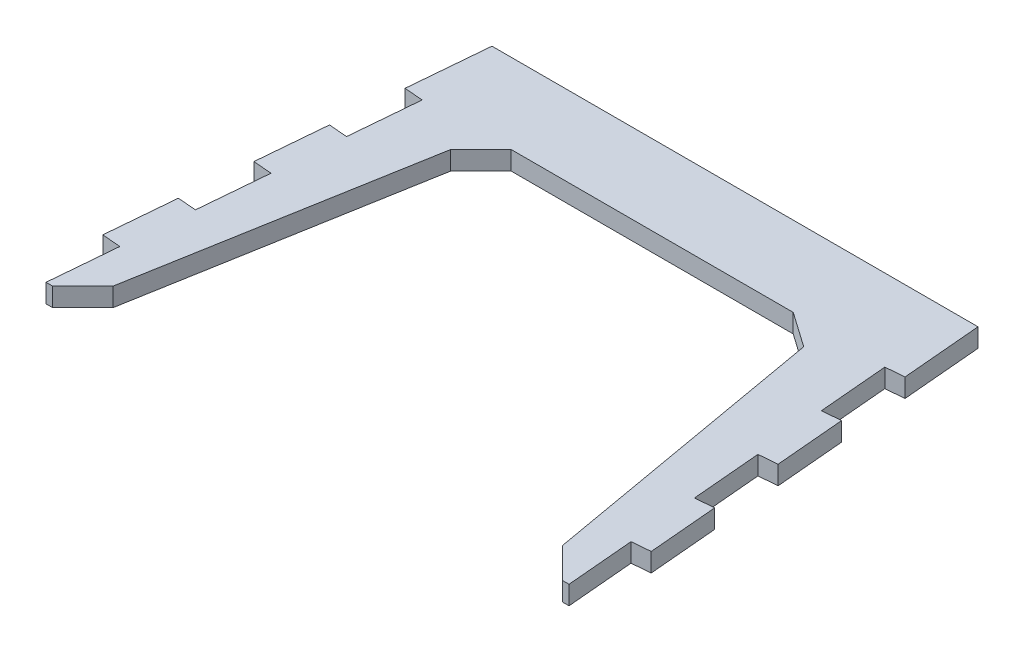
SolidWorks part; units mm, degrees
note: '?' marks a value the reader was unsure of.
ref_plane "Front Plane" through (0, 0, 0) normal (0, 0, 1) x (1, 0, 0)
ref_plane "Top Plane" through (0, 0, 0) normal (0, 1, 0) x (1, 0, 0)
ref_plane "Right Plane" through (0, 0, 0) normal (1, 0, 0) x (0, 0, -1)
ref_axis "Axis1" through (-195.3648, 0, -167.2622) along (0.0868, 0, -0.9962)?
ref_axis "Axis2" through (88.99, 0, -1387.812) along (0.0868, 0, 0.9962)?
sketch "Sketch2" plane through (0, 0, 0) normal (0, 1, 0) x (1, 0, 0)
  line L0 (-200.6811, 279.0317) -> (-224.9996, 0) construction
  line L1 (-224.9996, 0) -> (224.9996, 0) construction
  line L2 (224.9996, 0) -> (200.6811, 279.0317) construction
  line L3 (-135.5498, 279.0317) -> (-124.2612, 343.1772) construction
  line L4 (0, 0) -> (0, 279.0317) construction
  line L5 (0, 420.1319) -> (0, 0) construction
  line L6 (-188.3837, 420.1319) -> (-195.0906, 343.1772) construction
  line L7 (-195.0906, 343.1772) -> (-224.9996, 0)
  line L8 (-224.9996, 0) -> (-184.6548, 0)
  line L10 (-135.5498, 279.0317) -> (135.5498, 279.0317)
  line L11 (135.5498, 279.0317) -> (184.6548, 0)
  line L12 (184.6548, 0) -> (224.9996, 0)
  line L13 (224.9996, 0) -> (195.0906, 343.1772)
  line L14 (195.0906, 343.1772) -> (-195.0906, 343.1772)
  line L17 (-184.6548, 0) -> (-135.5498, 279.0317)
  line L19 (-204.9429, 0) -> (-168.3021, 279.0317) construction
  line L20 (-204.9429, 0) -> (-224.7726, 2.6039) construction
  line L21 (-135.5498, 279.0317) -> (-200.6811, 279.0317) construction
  dimension "D1" = 5
  dimension "D2" = 20
extrude "Boss-Extrude1" add sketch "Sketch2" against normal up to vertex (15 mm away)
chamfer "Chamfer1" distance 20 angle 45 2 edges at (-135.5498, -7.5, -279.0317) (135.5498, -7.5, -279.0317)
chamfer "Chamfer2" distance 20 angle 45 1 edges at (184.6548, -7.5, 0)
chamfer "Chamfer3" distance 20 angle 45 1 edges at (-184.6548, -7.5, 0)
sketch "Sketch3" plane through (0, 0, 0) normal (0, 1, 0) x (1, 0, 0)
  line L0 (-195.0906, 343.1772) -> (-224.9996, 0) construction
  line L1 (-224.9996, 0) -> (224.9996, 0) construction
  line L2 (224.9996, 0) -> (195.0906, 343.1772) construction
  line L3 (195.0906, 343.1772) -> (-195.0906, 343.1772) construction
  line L4 (-195.0906, 343.1772) -> (-224.9996, 0) construction
  line L5 (224.9996, 0) -> (195.0906, 343.1772) construction
  line L6 (195.0906, 343.1772) -> (-195.0906, 343.1772) construction
  line L7 (-224.9996, 0) -> (224.9996, 0) construction
  line L8 (-200.6811, 279.0317) -> (200.6811, 279.0317) construction
  line L9 (-135.5498, 279.0317) -> (135.5498, 279.0317) construction
  line L10 (-180.0333, 343.1772) -> (-209.9423, 0) construction
  line L11 (180.0333, 343.1772) -> (209.9423, 0) construction
  line L12 (-195.3648, 167.2622) -> (88.99, 3429.9628) construction
  line L13 (88.99, 1387.812) -> (195.3648, 167.2622) construction
  line L14 (0, 343.1772) -> (0, 0) construction
  line L15 (195.0906, 343.1772) -> (200.6811, 279.0317) construction
  line L16 (200.6811, 279.0317) -> (185.7373, 277.7293)
  line L17 (185.7373, 277.7293) -> (180.0333, 343.1772) construction
  line L18 (180.0333, 343.1772) -> (195.0906, 343.1772) construction
  line L19 (185.7373, 277.7293) -> (190.601, 221.923)
  line L20 (190.601, 221.923) -> (205.5448, 223.2254)
  line L21 (205.5448, 223.2254) -> (200.6811, 279.0317)
  line L22 (210.4085, 167.419) -> (195.4647, 166.1166)
  line L23 (195.4647, 166.1166) -> (200.3284, 110.3103)
  line L24 (200.3284, 110.3103) -> (215.2722, 111.6127)
  line L25 (215.2722, 111.6127) -> (210.4085, 167.419)
  line L26 (209.9423, 0) -> (224.9996, 0)
  line L27 (224.9996, 0) -> (220.1359, 55.8063)
  line L28 (220.1359, 55.8063) -> (205.1921, 54.5039)
  line L29 (205.1921, 54.5039) -> (209.9423, 0)
  line L30 (224.9996, 0) -> (195.0906, 343.1772) construction
  line L31 (212.664, 55.1551) -> (207.8003, 110.9615) construction
  line L32 (202.9366, 166.7678) -> (198.0729, 222.5742) construction
extrude "Cut-Extrude1" cut sketch "Sketch3" against normal through all
mirror "Mirror1" about plane through (0, 0, 0) normal (1, 0, 0) of "Cut-Extrude1"
